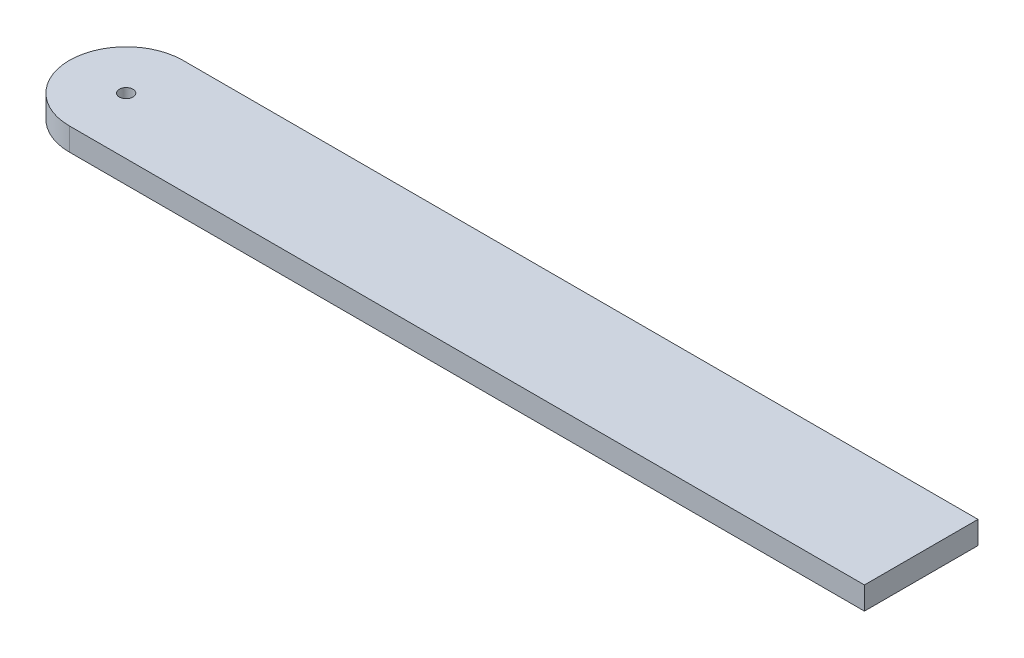
SolidWorks part; units mm, degrees
ref_plane "Front Plane" through (0, 0, 0) normal (0, 0, 1) x (1, 0, 0)
ref_plane "Top Plane" through (0, 0, 0) normal (0, 1, 0) x (1, 0, 0)
ref_plane "Right Plane" through (0, 0, 0) normal (1, 0, 0) x (0, 0, -1)
sketch "Sketch1" plane through (0, 0, 0) normal (0, 1, 0) x (1, 0, 0)
  line L1 (0, -5) -> (70, -5)
  line L2 (0, -5) -> (0, 5)
  line L3 (0, 5) -> (70, 5)
  line L4 (70, -5) -> (70, 5)
  circle A0 centre (0, 0) radius 5
  dimension "D1" = 10
  dimension "D2" = 70
extrude "Boss-Extrude1" add sketch "Sketch1" along normal blind 2 contours A0 L1 L4 L3 | L2 A0 | L2 A0 region at (36.9541, 0, 0) region at (-2.1221, 0, 0) region at (2.1221, 0, 0)
sketch "Sketch2" plane through (0, 2, 0) normal (0, 1, 0) x (1, 0, 0)
  circle A0 centre (0, 0) radius 0.6
extrude "Cut-Extrude1" cut sketch "Sketch2" against normal blind 1.6
